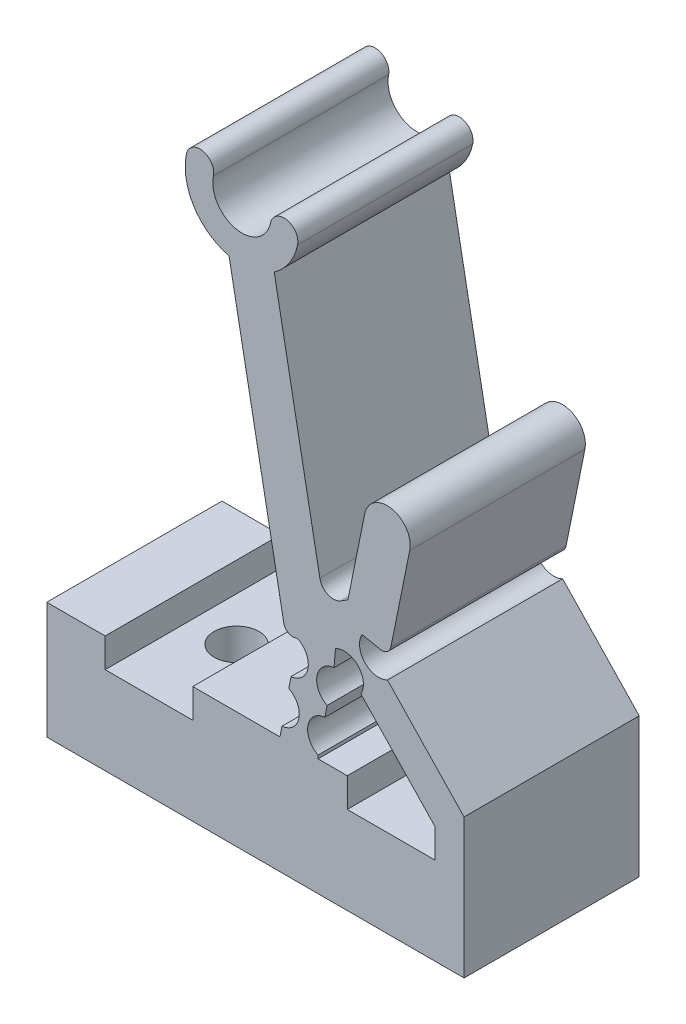
SolidWorks part; units mm, degrees
ref_plane "Front Plane" through (0, 0, 0) normal (0, 0, 1) x (1, 0, 0)
ref_plane "Top Plane" through (0, 0, 0) normal (0, 1, 0) x (1, 0, 0)
ref_plane "Right Plane" through (0, 0, 0) normal (1, 0, 0) x (0, 0, -1)
sketch "Sketch-SkeletonConfigUp" plane through (0, 0, 0) normal (0, 0, 1) x (1, 0, 0)
  line L0 (0, 0) -> (0, -50000) construction
  line L1 (0, 0) -> (7.455, 0.2734) construction
  line L2 (9.9233, 0.3639) -> (10.6101, 4.558) construction
  line L3 (10.6101, 4.558) -> (7.9471, 2.8569) construction
  line L4 (7.9471, 2.8569) -> (7.455, 0.2734) construction
  line L5 (10.6101, 4.558) -> (12.0093, 11.478) construction
  line L6 (7.9471, 2.8569) -> (4.1146, 23.199) construction
  line L7 (7.455, 0.2734) -> (9.9233, 0.3639) construction
  line L8 (-989.4051, -36.2798) -> (9.9233, 0.3639) construction
  dimension "D2" = 7.46
  dimension "D3" = 2.47
  dimension "D4" = 4.25
  dimension "D5" = 78.6
  dimension "D6" = 3.16
  dimension "D7" = 7.06
  dimension "D8" = 20.7
  dimension "D9" = 2.63
  dimension "D10" = 46
  dimension "D11" = 111.9
  dimension "D12" = 92.1
sketch "Sketch-SkeletonConfigDown" plane through (0, 0, 0) normal (0, 0, 1) x (1, 0, 0)
  line L0 (0, 0) -> (0, -50000) construction
  line L1 (0, 0) -> (7.455, 0.2734) construction
  line L2 (9.9233, 0.3639) -> (10.6101, 4.558) construction
  line L3 (10.6101, 4.558) -> (9.7761, 1.5101) construction
  line L4 (9.7761, 1.5101) -> (7.455, 0.2734) construction
  line L5 (10.6101, 4.558) -> (7.0062, 10.6288) construction
  line L6 (9.7761, 1.5101) -> (-6.7111, 14.0265) construction
  line L7 (7.455, 0.2734) -> (9.9233, 0.3639) construction
  line L8 (-993.745, -36.439) -> (9.9233, 0.3639) construction
  dimension "D2" = 7.46
  dimension "D3" = 2.47
  dimension "D4" = 4.25
  dimension "D5" = 78.6
  dimension "D6" = 3.16
  dimension "D7" = 7.06
  dimension "D8" = 20.7
  dimension "D9" = 2.63
  dimension "D10" = 46
  dimension "D11" = 111.9
  dimension "D1" = 92.1
sketch "Sketch-ConfigDown" plane through (0, 0, 0) normal (0, 0, 1) x (1, 0, 0)
  line L3 (7.5052, -0.2251) -> (4.7337, -0.3268) construction
  line L4 (9.7761, 1.5101) -> (-6.7111, 14.0265) construction
  line L6 (-200859.4238, -7365.1807) -> (9.9233, 0.3639) construction
  line L7 (7.5052, -0.2251) -> (15.9124, 0.0831) construction
  line L9 (7.455, 0.2734) -> (9.9233, 0.3639) construction
  line L10 (10.9008, 0.9001) -> (10.9374, -0.0993) construction
  line L15 (9.4668, 0.4955) -> (8.4696, -0.0359)
  line L18 (8.3945, 1.6237) -> (9.0998, 0.2999) construction
  line L19 (6.3613, 10.246) -> (8.7382, 6.242)
  line L20 (-5.5253, 12.1846) -> (7.951, 1.954)
  line L21 (8.058, 3.756) -> (-4.6183, 13.3794)
  line L22 (9.7761, 1.5101) -> (7.455, 0.2734) construction
  line L23 (2.778, 5.8811) -> (3.685, 7.0758) construction
  line L26 (10.6101, 4.558) -> (14.4503, 0.5299) construction
  line L27 (10.0779, 5.4546) -> (9.138, 2.0199) construction
  line L28 (11.1752, 5.0523) -> (15.9124, 0.0831) construction
  line L29 (14.3773, -0.4805) -> (10.5848, 3.4977) construction
  line L30 (12.8137, 1.1596) -> (13.8994, 2.1946) construction
  line L34 (4.7337, -0.3268) -> (4.7337, -3.5018) construction
  line L36 (4.7337, -3.5018) -> (15.9124, -3.5018)
  line L37 (15.9124, -3.5018) -> (15.9124, 0.0831)
  line L38 (-8.0357, 12.2817) -> (-6.0162, 14.9419) construction
  line L39 (10.6101, 4.558) -> (9.7761, 1.5101) construction
  line L40 (9.5145, 3.3957) -> (10.9613, 2.9997) construction
  line L42 (7.6511, 11.0117) -> (10.5812, 6.0759)
  line L43 (7.8883, 7.6738) -> (9.1781, 8.4395) construction
  line L44 (10.6101, 4.558) -> (7.0062, 10.6288) construction
  line L45 (7.4964, -0.3268) -> (4.7337, -0.3268) construction
  line L46 (14.3773, -0.4805) -> (15.9124, -0.4805) construction
  line L47 (12.9938, -0.3268) -> (7.4964, -0.3268)
  line L48 (8.7382, 6.242) -> (8.058, 3.756)
  line L49 (15.9124, 0.0831) -> (15.463, 0.5545)
  line L50 (10.5848, 3.4977) -> (9.5498, 4.5833) construction
  line L51 (15.463, 0.5545) -> (14.3773, -0.4805) construction
  line L52 (14.7645, 0.9249) -> (14.9455, 1.0974) construction
  line L53 (13.3423, 0.6052) -> (14.428, 1.6402) construction
  line L54 (11.1752, 5.0523) -> (10.6355, 5.6184) construction
  line L55 (10.972, 4.903) -> (11.153, 5.0755) construction
  line L56 (9.5498, 4.5833) -> (10.6355, 5.6184) construction
  line L57 (10.5848, 3.4977) -> (11.6705, 4.5327) construction
  line L58 (10.972, 4.903) -> (10.2482, 4.213) construction
  line L59 (11.6705, 4.5327) -> (14.428, 1.6402)
  line L60 (13.3423, 0.6052) -> (10.5848, 3.4977)
  line L61 (10.6355, 5.6184) -> (10.5812, 6.0759)
  line L62 (7.245, 0.6675) -> (7.1274, 0.8882) construction
  line L63 (7.1458, -0.7412) -> (6.4216, -1.127) construction
  line L64 (7.7642, 1.2879) -> (8.4696, -0.0359) construction
  line L65 (6.4404, 0.5826) -> (7.1458, -0.7412) construction
  line L66 (6.4404, 0.5826) -> (4.7337, -0.3268)
  line L67 (6.4404, 0.5826) -> (7.7642, 1.2879) construction
  line L68 (7.245, 0.6675) -> (7.665, -0.1208) construction
  line L69 (10.0853, 2.5247) -> (10.6904, 2.847) construction
  line L70 (10.7907, 1.2008) -> (11.23, 1.4349) construction
  line L71 (9.5602, 1.9151) -> (9.4427, 2.1358) construction
  line L72 (8.7615, 1.8193) -> (9.4668, 0.4955) construction
  line L73 (10.0853, 2.5247) -> (10.7907, 1.2008) construction
  line L74 (9.5602, 1.9151) -> (9.9919, 1.105) construction
  line L75 (7.7642, 1.2879) -> (8.7615, 1.8193)
  line L76 (7.951, 1.954) -> (9.2805, 2.6624)
  line L77 (9.4615, 3.9513) -> (10.971, 2.3679)
  line L78 (10.971, 2.3679) -> (11.066, 2.2683)
  line L79 (-6.7111, 14.0265) -> (-5.0362, 14.2558) construction
  line L80 (-6.7111, 14.0265) -> (-6.7111, -3.5018) construction
  line L81 (4.7337, -3.5018) -> (-6.7111, -3.5018)
  line L82 (-6.7111, -3.5018) -> (-6.7111, -0.3268)
  line L83 (-6.7111, -0.3268) -> (4.7337, -0.3268)
  line L84 (8.7615, 1.8193) -> (10.0853, 2.5247) construction
  arc A2 (-7.4311, 13.0782) -> (-5.5316, 14.188) centre (-6.7111, 14.0265) ccw
  arc A3 (-4.6183, 13.3794) -> (-4.5408, 14.3236) centre (-6.7111, 14.0265) ccw
  arc A4 (-8.0357, 12.2817) -> (-7.4311, 13.0782) centre (-7.7334, 12.68) cw
  arc A5 (-4.5408, 14.3236) -> (-5.5316, 14.188) centre (-5.0362, 14.2558) ccw
  arc A6 (-8.0357, 12.2817) -> (-5.5253, 12.1846) centre (-6.7111, 14.0265) ccw
  arc A7 (6.3613, 10.246) -> (7.6511, 11.0117) centre (7.0062, 10.6288) cw
  arc A8 (15.463, 0.5545) -> (14.428, 1.6402) centre (15.6693, 1.7874) cw
  arc A9 (14.3773, -0.4805) -> (13.3423, 0.6052) centre (13.136, -0.6277) ccw
  arc A10 (10.6355, 5.6184) -> (11.6705, 4.5327) centre (11.8768, 5.7655) ccw
  arc A11 (9.5498, 4.5833) -> (10.5848, 3.4977) centre (9.3435, 3.3505) cw
  arc A12 (7.7642, 1.2879) -> (6.4404, 0.5826) centre (6.7377, 1.6196) cw
  arc A13 (7.1458, -0.7412) -> (8.4696, -0.0359) centre (8.1723, -1.0729) cw
  arc A14 (7.1458, -0.7412) -> (7.4964, -0.3268) centre (7.8257, -0.9609) ccw
  arc A15 (8.7615, 1.8193) -> (10.0853, 2.5247) centre (9.0374, 2.8965) ccw
  arc A16 (9.4668, 0.4955) -> (10.7907, 1.2008) centre (10.5148, 0.1237) cw
  arc A19 (10.0853, 2.5247) -> (9.2805, 2.6624) centre (9.6949, 2.6632) ccw
  arc A20 (14.3773, -0.4805) -> (12.9938, -0.3268) centre (13.6677, -0.5646) cw
  arc A21 (9.5498, 4.5833) -> (9.4615, 3.9513) centre (9.4971, 4.2685) ccw
  arc A22 (10.7907, 1.2008) -> (11.066, 2.2683) centre (10.9274, 1.7348) ccw
  point P24 (8.7471, 0.9618)
  point P28 (10.9191, 0.4004)
  point P30 (8.5332, 8.0566)
  point P43 (10.2379, 3.1977)
  point P47 (14.7645, 0.9249)
  point P51 (3.2315, 6.4785)
  point P61 (13.3566, 1.6771)
  dimension "D12" = 1.5
  dimension "D3" = 2.3812
  dimension "D4" = 4.3812
  dimension "D1" = 1
  dimension "D5" = 1.5
  dimension "D6" = 7
  dimension "D2" = 3.175
  dimension "D7" = 1.5
  dimension "D9" = 1.5
  dimension "D10" = 0.25
  dimension "D8" = 1.5
  dimension "D11" = 1.5
  dimension "D13" = 0.5
  dimension "D14" = 0.5
  dimension "D15" = 45
sketch "Sketch-ConfigUp" plane through (0, 0, 0) normal (0, 0, 1) x (1, 0, 0)
  line L1 (6.7776, 2.0617) -> (6.6598, 1.4428)
  line L4 (7.9471, 2.8569) -> (7.455, 0.2734) construction
  line L5 (10.7841, 11.7257) -> (9.8745, 7.2272)
  line L6 (7.455, 0.2734) -> (9.9233, 0.3639) construction
  line L9 (10.6101, 4.558) -> (7.9471, 2.8569) construction
  line L10 (7.1519, 4.0264) -> (6.4787, 3.8995)
  line L11 (6.7187, 1.7522) -> (8.6834, 1.378) construction
  line L12 (12.1113, 5.6751) -> (10.6439, 5.9718)
  line L16 (12.024, 4.5242) -> (10.6439, 5.9718) construction
  line L17 (13.2345, 11.2303) -> (12.1113, 5.6751)
  line L18 (10.6101, 4.558) -> (12.0093, 11.478) construction
  line L19 (10.315, 9.4057) -> (12.7654, 8.9103) construction
  line L20 (3.4089, 20.1933) -> (6.4787, 3.8995)
  line L21 (8.5546, 6.384) -> (5.8657, 20.6561)
  line L22 (7.9471, 2.8569) -> (4.1146, 23.199) construction
  line L23 (5.3299, 9.997) -> (7.7867, 10.4599) construction
  line L26 (11.3002, 3.8342) -> (14.4503, 0.5299) construction
  line L27 (-200855.0838, -7365.0216) -> (9.9233, 0.3639) construction
  line L30 (12.336, 1.2984) -> (13.7836, 2.6784) construction
  line L38 (2.5546, 22.9051) -> (4.1146, 23.199) construction
  line L39 (4.1146, 23.199) -> (7.1366, 22.5661) construction
  line L42 (9.8377, -1.0766) -> (9.8377, -7.4266) construction
  line L43 (9.1963, 4.5918) -> (10.6439, 5.9718) construction
  line L44 (7.6421, 1.2557) -> (7.2679, -0.709) construction
  line L46 (8.6244, 1.0686) -> (8.2502, -0.8961) construction
  line L47 (10.5764, 3.1442) -> (12.024, 4.5242) construction
  line L48 (16.1877, 0.1566) -> (12.024, 4.5242)
  line L51 (7.7015, 2.9037) -> (8.1927, 2.8101) construction
  line L52 (6.7776, 2.0617) -> (8.7423, 1.6875) construction
  line L53 (7.1519, 4.0264) -> (9.1165, 3.6521) construction
  line L54 (14.6002, -1.0766) -> (14.6002, -7.4266) construction
  line L56 (7.76, 1.8746) -> (8.1342, 3.8393) construction
  line L59 (7.1519, 4.0264) -> (6.7776, 2.0617) construction
  line L61 (8.7423, 1.6875) -> (8.6244, 1.0686)
  line L62 (6.6598, 1.4428) -> (8.6244, 1.0686) construction
  line L67 (4.1146, 23.199) -> (1.0927, 23.832) construction
  line L69 (10.7911, 4.7305) -> (10.4292, 4.3855) construction
  line L71 (10.6439, 5.9718) -> (9.6089, 7.0575) construction
  line L73 (6.6598, 1.4428) -> (6.2855, -0.5219) construction
  line L77 (14.4503, 0.5299) -> (9.9233, 0.3639) construction
  line L78 (9.1963, 4.5918) -> (9.1165, 3.6521)
  line L79 (8.5546, 6.384) -> (9.8745, 7.2272)
  line L81 (11.3002, 3.8342) -> (9.9201, 5.2818) construction
  line L82 (10.315, 9.4057) -> (9.8745, 7.2272) construction
  line L92 (9.8377, -1.0766) -> (14.6002, -1.0766)
  line L93 (7.2094, 0.3201) -> (7.7006, 0.2266) construction
  line L94 (16.1877, -7.4266) -> (16.1877, 0.1566)
  line L107 (6.1799, -1.0766) -> (-6.5007, -1.0766)
  line L108 (-6.5007, -1.0766) -> (-6.5007, -7.4266)
  line L109 (-6.5007, -7.4266) -> (16.1877, -7.4266)
  line L115 (6.2855, -0.5219) -> (6.1799, -1.0766)
  line L116 (12.8073, 0.8041) -> (10.5764, 3.1442)
  line L117 (10.5764, 3.1442) -> (9.1963, 4.5918) construction
  line L121 (9.1165, 3.6521) -> (8.7423, 1.6875) construction
  line L125 (8.2502, -0.8961) -> (8.2502, -1.0766)
  line L126 (12.8073, 0.8041) -> (14.6002, -1.0766)
  line L128 (8.5546, 6.384) -> (9.0675, 3.6615) construction
  line L129 (6.2855, -0.5219) -> (8.2502, -0.8961) construction
  line L130 (8.2502, -1.0766) -> (9.8377, -1.0766)
  line L131 (14.6002, -1.0766) -> (16.1877, -1.0766) construction
  arc A0 (10.7841, 11.7257) -> (13.2345, 11.2303) centre (12.0093, 11.478) cw
  arc A2 (2.5609, 23.5245) -> (5.6684, 22.8736) centre (4.1146, 23.199) ccw
  arc A3 (5.8657, 20.6561) -> (7.1366, 22.5661) centre (4.1146, 23.199) ccw
  arc A4 (1.0927, 23.832) -> (2.5609, 23.5245) centre (1.8268, 23.6783) cw
  arc A5 (7.1366, 22.5661) -> (5.6684, 22.8736) centre (6.4025, 22.7198) ccw
  arc A6 (1.0927, 23.832) -> (3.4089, 20.1933) centre (4.1146, 23.199) ccw
  arc A7 (8.7423, 1.6875) -> (9.1165, 3.6521) centre (9.2159, 2.6152) cw
  arc A15 (8.6244, 1.0686) -> (8.2502, -0.8961) centre (8.7238, 0.0317) ccw
  arc A21 (6.7776, 2.0617) -> (7.1519, 4.0264) centre (6.6782, 3.0986) ccw
  arc A42 (6.6598, 1.4428) -> (6.2855, -0.5219) centre (6.1861, 0.515) cw
  arc A43 (12.024, 4.5242) -> (10.6439, 5.9718) centre (11.545, 5.4493) cw
  arc A44 (10.5764, 3.1442) -> (9.1963, 4.5918) centre (9.6752, 3.6667) ccw
  point P27 (7.701, 1.5651)
  point P38 (11.5402, 9.158)
  point P51 (6.5583, 10.2285)
  point P61 (13.0598, 1.9884)
  point P125 (7.7006, 0.2266)
  point P130 (7.2094, 0.3201)
  dimension "D3" = 3.175
  dimension "D4" = 6.175
  dimension "D5" = 7
  dimension "D14" = 22.5
  dimension "D21" = 22.5
  dimension "D22" = 2
  dimension "D24" = 0.5
  dimension "D8" = 4.7625
  dimension "D9" = 2
  dimension "D10" = 2
  dimension "D11" = 0.5
  dimension "D6" = 2
  dimension "D7" = 0.5
  dimension "D12" = 1.5
  dimension "D16" = 2.5
  dimension "D13" = 1.5875
  dimension "D15" = 6.35
extrude "Boss-ConfigUp" add sketch "Sketch-ConfigUp" along normal blind 9.525
sketch "Sketch2" plane through (0.0043, -1.0766, 0) normal (0, -1, 0) x (-1, 0, 0)
  line L0 (6.505, -9.525) -> (-16.1834, -9.525) construction
  line L1 (-14.5959, 0) -> (-9.8334, 0)
  line L2 (-14.5959, 0) -> (-14.5959, -9.525)
  line L3 (-14.5959, -9.525) -> (-9.8334, -9.525)
  line L4 (-9.8334, 0) -> (-9.8334, -9.525)
  line L12 (-14.5959, 0) -> (-9.8334, -9.525) construction
  line L17 (-14.5959, -9.525) -> (-9.8334, 0) construction
  line L18 (6.505, 0) -> (-16.1834, 0) construction
  line L19 (6.505, -9.525) -> (6.505, 0) construction
  line L20 (3.33, -9.525) -> (3.33, 0)
  line L21 (3.33, -9.525) -> (-1.4325, -9.525)
  line L22 (3.33, 0) -> (-1.4325, 0)
  line L23 (-1.4325, -9.525) -> (-1.4325, 0)
  line L24 (3.33, -9.525) -> (-1.4325, 0) construction
  line L25 (3.33, 0) -> (-1.4325, -9.525) construction
  line L26 (6.505, -9.525) -> (-16.1834, -9.525) construction
  point P4 (-12.2147, -4.7625)
  point P26 (0.9487, -4.7625)
  dimension "D1" = 4.7625
  dimension "D2" = 3.175
extrude "Cut-NutSlot" cut sketch "Sketch2" along normal blind 1.5875
hole_wizard "#2 Clearance Hole1" positions "Sketch4" profile "Sketch3" hole size "#2" standard "ANSI Inch" end condition up to next
sketch "Sketch4" plane through (0, -7.4266, 0) normal (0, -1, 0) x (-1, 0, 0)
  line L16 (-14.6002, 0) -> (-9.8377, -9.525) construction
  point P40 (-12.219, -4.7625)
  point P44 (0.9444, -4.7625)
sketch "Sketch3" plane through (12.219, -7.4266, 4.7625) normal (1, 0, 0) x (0, 0, -1)
  line L0 (0, 0) -> (0, 4.7625)
  line L1 (0, 4.7625) -> (1.2192, 4.7625)
  line L2 (1.2192, 4.7625) -> (1.2192, 0)
  line L5 (1.2192, 0) -> (0, 0)
  line L11 (0, -6.35) -> (0, 107.95) construction
  dimension "Thru Hole Dia." = 2.4384
  dimension "Thru Hole Depth" = 4.7625
ref_plane "Plane-Midplane" through (0, 0, 4.7625) normal (0, 0, -1) x (-1, 0, 0)
fillet "Fillet1" radius 0.5 2 edges at (12.1113, 5.6751, 4.7625) (6.4787, 3.8995, 4.7625)
fillet "Fillet2" radius 0.75 1 edges at (8.5546, 6.384, 4.7625)
ref_axis "Axis-CableUp" through (4.1146, 23.199, 9.525) along (0, 0, -1)
ref_axis "Axis-CableDown" through (-6.7111, 14.0265, 0) along (0, 0, 1)
sketch "Sketch5" plane through (0, 0, 0) normal (0, 0, 1) x (1, 0, 0)
  point P0 (-6.7111, 14.0265)
  point P2 (4.1146, 23.199)
  dimension "D1" = 9.1725
  dimension "D2" = 10.8258
equation "\"axle-diameter\"=2"
equation "\"switch-thickness\"=12"
equation "\"base-width\"=4.0"
equation "\"axle-bushing-radius\"=3"
equation "\"clearance\"= 0.25"
equation "\"arm-width\"=1.5"
equation "\"min-diameter\"=70"
equation "\"alpha\"=92.1"
equation "\"beta\"=26.0"
equation "\"gamma\"=78.6"
equation "\"delta\"=111.9"
equation "\"epsilon\"=46.0"
equation "\"eta\"=-228.1"
equation "\"l_AB\"=2.47"
equation "\"l_AC\"=2.63"
equation "\"l_BD\"=4.25"
equation "\"l_CD\"=3.16"
equation "\"l_CE\"=20.70"
equation "\"l_DF\"=7.06"
equation "\"l_OA\"=7.46"
equation "\"D2@Sketch-SkeletonConfigUp\" = \"l_OA\""
equation "\"D3@Sketch-SkeletonConfigUp\" = \"l_AB\""
equation "\"D4@Sketch-SkeletonConfigUp\" = \"l_BD\""
equation "\"D5@Sketch-SkeletonConfigUp\" = \"gamma\""
equation "\"D6@Sketch-SkeletonConfigUp\" = \"l_CD\""
equation "\"D7@Sketch-SkeletonConfigUp\" = \"l_DF\""
equation "\"D8@Sketch-SkeletonConfigUp\" = \"l_CE\""
equation "\"D9@Sketch-SkeletonConfigUp\" = \"l_AC\""
equation "\"D_groove\"=3.175"
equation "\"D3@Sketch-ConfigUp\" = \"D_groove\""
equation "\"D4@Sketch-ConfigUp\" = \"D_groove\" + 2 * \"arm-width\""
equation "\"D7@Sketch-SkeletonConfigDown\" = \"l_DF\""
equation "\"D6@Sketch-SkeletonConfigDown\" = \"l_CD\""
equation "\"D2@Sketch-SkeletonConfigDown\" = \"l_OA\""
equation "\"D3@Sketch-SkeletonConfigDown\" = \"l_AB\""
equation "\"D9@Sketch-SkeletonConfigDown\" = \"l_AC\""
equation "\"D8@Sketch-SkeletonConfigDown\" = \"l_CE\""
equation "\"D5@Sketch-SkeletonConfigDown\" = \"gamma\""
equation "\"D4@Sketch-SkeletonConfigDown\" = \"l_BD\""
equation "\"D1@Sketch-SkeletonConfigDown\" = \"alpha\""
equation "\"D5@Sketch-ConfigDown\" = \"arm-width\""
equation "\"hinge_length\"=1.5"
equation "\"hinge_depth\"=0.25"
equation "\"D9@Sketch-ConfigDown\" = \"hinge_length\""
equation "\"D10@Sketch-ConfigDown\" = \"hinge_depth\""
equation "\"D8@Sketch-ConfigDown\" = \"hinge_length\""
equation "\"D11@Sketch-ConfigDown\" = \"hinge_length\""
equation "\"D12@Sketch-ConfigDown\" = \"hinge_length\""
equation "\"D10@Sketch-SkeletonConfigUp\"=\"epsilon\""
equation "\"D11@Sketch-SkeletonConfigUp\"=\"delta\""
equation "\"D12@Sketch-SkeletonConfigUp\"=\"alpha\""
equation "\"D11@Sketch-SkeletonConfigDown\"=\"delta\""
equation "\"D10@Sketch-SkeletonConfigDown\"=\"epsilon\""
